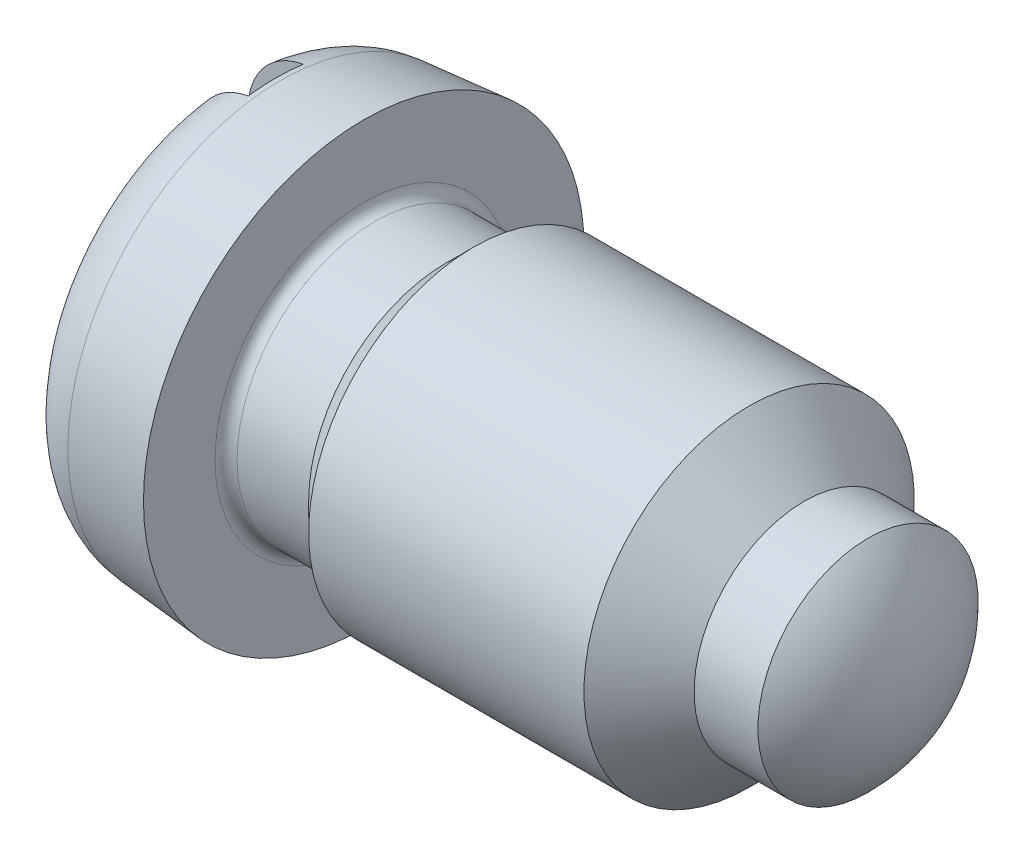
SolidWorks part; units mm, degrees
ref_plane "Front" through (0, 0, 0) normal (0, 0, 1) x (1, 0, 0)
ref_plane "Top" through (0, 0, 0) normal (0, 1, 0) x (1, 0, 0)
ref_plane "Right" through (0, 0, 0) normal (1, 0, 0) x (0, 0, -1)
sketch "Sketch1" plane through (0, 0, 0) normal (0, 0, 1) x (1, 0, 0)
  line L0 (1.3, 1.5) -> (4.8, 1.5)
  line L1 (4.8, 1.5) -> (5.3, 1)
  line L2 (5.3, 1) -> (5.8798, 1)
  line L3 (1.3, 0) -> (7.8489, 0) construction
  line L4 (1.3, 1.5) -> (1.3, 2)
  line L5 (1.3, 2) -> (0, 1.8863)
  line L6 (0, 0) -> (0, 1.8863)
  line L7 (6.3, 0) -> (0, 0)
  arc A0 (5.8798, 1) -> (6.3, 0) centre (4.9, 0) cw
  dimension "D3" = 135
  dimension "D7" = 5
revolve "Base" add sketch "Sketch1" angle 360 about L3
cosmetic thread "ThreadCosmetic1" [suppressed] parameters "b"=3.9, "D2"=2
fillet "Fillet1" radius 0.6 1 edges at (0, -1.8863, 0)
sketch "Sketch3" plane through (0, 0, 0) normal (0, 0, 1) x (1, 0, 0)
  line L0 (1.3, 2) -> (1.3, 1.25)
  line L1 (1.3, -2) -> (1.3, 2) construction
  line L2 (1.3, 1.5) -> (4.8, 1.5) construction
  line L3 (2.3, 1.5) -> (2.3, 2)
  line L4 (2.3, 2) -> (1.3, 2)
  line L5 (0, 0) -> (2.9582, 0) construction
  line L6 (0, 1.3365) -> (0, -1.3365) construction
  line L7 (6.3, 0) -> (0, 0) construction
  line L8 (2.3, 1.5) -> (2.05, 1.25)
  line L9 (2.05, 1.25) -> (1.3, 1.25)
  dimension "D2" = 45
  dimension "D3" = 2.5
revolve "Cut-Revolve1" cut sketch "Sketch3" angle 360 about L5
fillet "Fillet2" radius 0.1 1 edges at (1.3, -1.25, 0)
sketch "Sketch2" plane through (0, 0, 0) normal (0, -1, 0) x (-1, 0, 0)
  line L0 (-1.6311, 0) -> (0.8061, 0) construction
  line L3 (0, -0.25) -> (-0.5, -0.25)
  line L4 (0, -0.25) -> (0, 0.25)
  line L5 (0, 0.25) -> (-0.5, 0.25)
  line L6 (-0.5, -0.25) -> (-0.5, 0.25)
  dimension "n" = 0.5
  dimension "t" = 0.5
extrude "Slot" cut sketch "Sketch2" against normal through all and the other way through all
sketch "Sketch4" plane through (0, 0, 0) normal (0, 0, 1) x (1, 0, 0)
  line L0 (4.8, 1.067) -> (5.05, 1.5)
  line L1 (5.05, 1.5) -> (5.05, 2)
  line L2 (5.05, 2) -> (4.55, 2)
  line L3 (4.55, 2) -> (4.55, 1.5)
  line L4 (4.55, 1.5) -> (4.8, 1.067)
  line L5 (4.8, -1.5) -> (4.8, 1.5) construction
  line L6 (4.8, 1.5) -> (2.3, 1.5) construction
  line L7 (0, 0) -> (8.3043, 0) construction
  line L8 (0, 1.3129) -> (0, -1.3129) construction
revolve "Cut-Revolve10" [suppressed] cut sketch "Sketch4" angle 360 about L7
pattern_linear "LPattern10" [suppressed] count 5 spacing 0.6 along (-1, 0, 0) of bodies 104
equation "\"D3@Sketch3\" =  ( \"d@Sketch1\" + \"D2@ThreadCosmetic1\" )  / 2"
equation "\"D1@Sketch4\" =  ( \"d@Sketch1\" - \"D2@ThreadCosmetic1\" )  / 2"
equation "\"D3@LPattern10\" = \"D1@Sketch4\" * 1.2"
equation "\"D1@LPattern10\" =  ( \"l@Sketch1\" - \"a@Sketch3\" )  / \"D3@LPattern10\""
